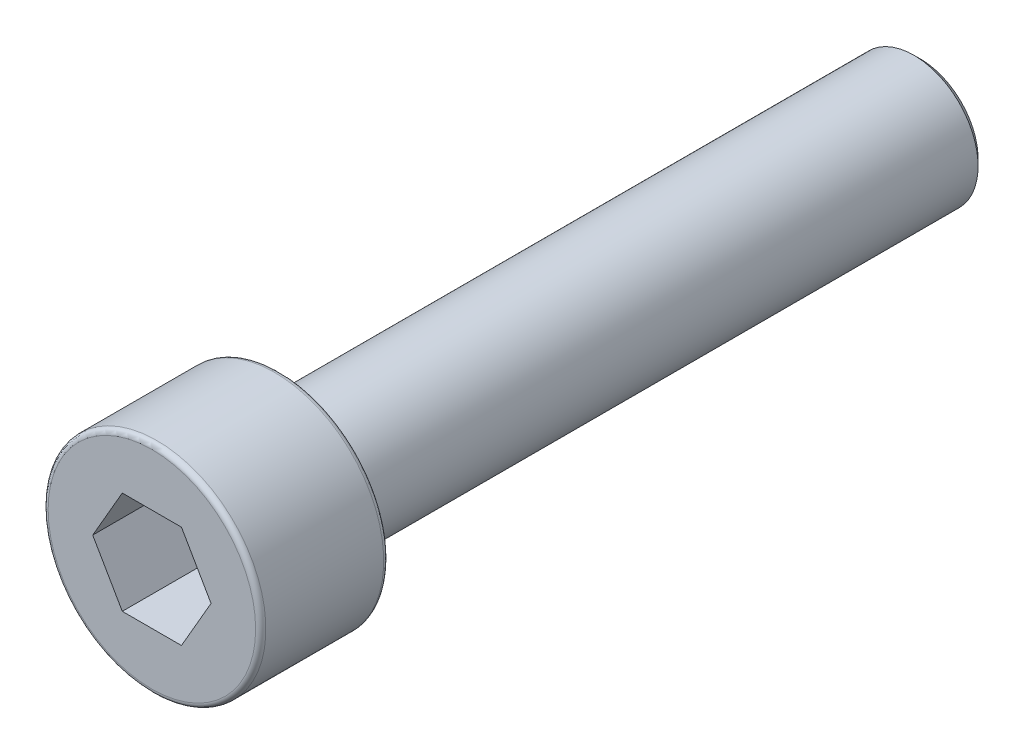
SolidWorks part; units mm, degrees
ref_plane "Front Plane" through (0, 0, 0) normal (0, 0, 1) x (1, 0, 0)
ref_plane "Top Plane" through (0, 0, 0) normal (0, 1, 0) x (1, 0, 0)
ref_plane "Right Plane" through (0, 0, 0) normal (1, 0, 0) x (0, 0, -1)
ref_plane "Plane1" through (0, 0, 30) normal (0, 0, 1) x (1, 0, 0)
sketch "Sketch1" plane through (0, 0, 30) normal (0, 0, 1) x (1, 0, 0)
  circle A0 centre (0, 0) radius 4.25
extrude "Boss-Extrude1" add sketch "Sketch1" against normal blind 5
sketch "Sketch2" plane through (0, 0, 25) normal (0, 0, -1) x (-1, 0, 0)
  circle A0 centre (0, 0) radius 2.5
extrude "Boss-Extrude2" add sketch "Sketch2" along normal blind 25
sketch "Sketch3" plane through (0, 0, 30) normal (0, 0, 1) x (1, 0, 0)
  line L0 (-2.3094, 0) -> (-1.1547, -2)
  line L1 (-1.1547, -2) -> (1.1547, -2)
  line L2 (1.1547, -2) -> (2.3094, 0)
  line L3 (2.3094, 0) -> (1.1547, 2)
  line L4 (1.1547, 2) -> (-1.1547, 2)
  line L5 (-1.1547, 2) -> (-2.3094, 0)
extrude "Cut-Extrude1" cut sketch "Sketch3" against normal blind 4
chamfer "Chamfer1" distance 0.25 angle 45 1 edges at (-2.5, 0, 0)
fillet "Fillet1" radius 0.2 2 edges at (-4.25, 0, 25) (-4.25, 0, 30) tangent propagation no
ref_axis "Axis1" through (0, 0, -2.3129) along (0, 0, 1)
